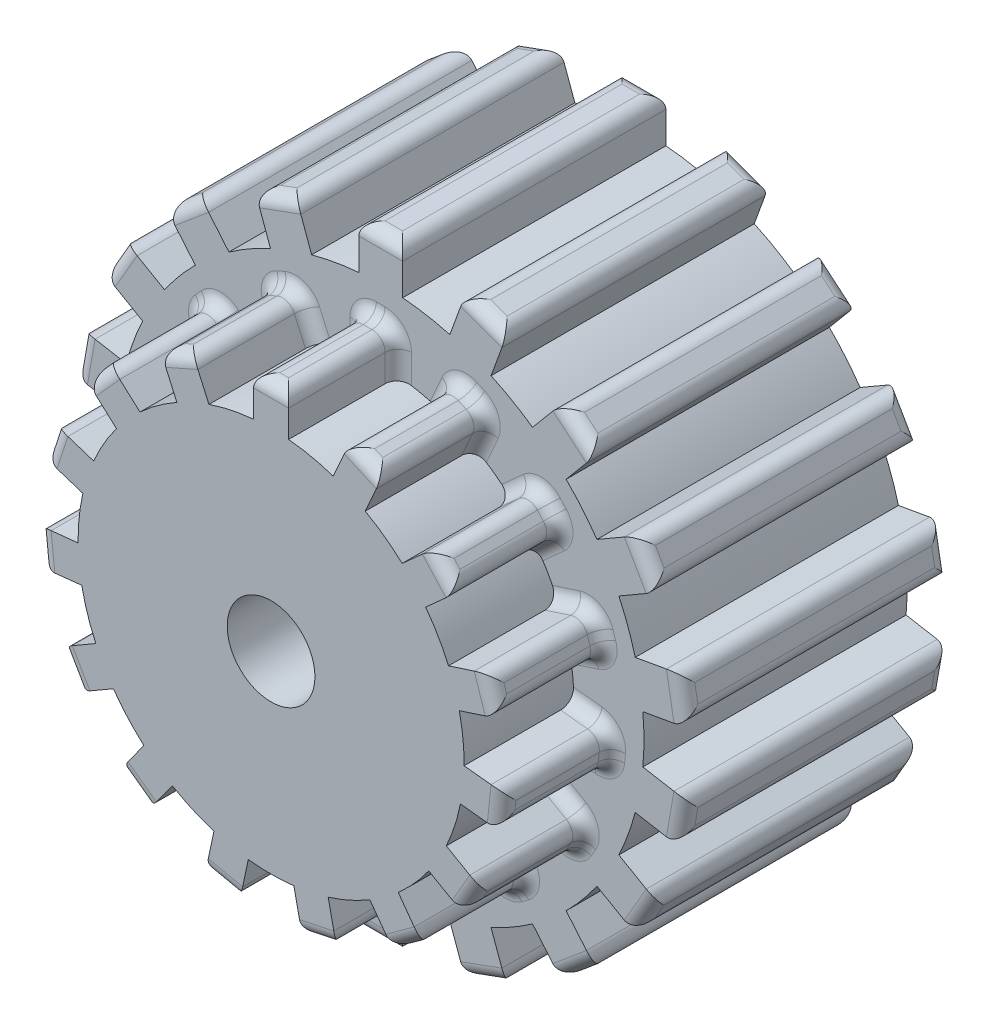
SolidWorks part; units mm, degrees
ref_plane "Front Plane" through (0, 0, 0) normal (0, 0, 1) x (1, 0, 0)
ref_plane "Top Plane" through (0, 0, 0) normal (0, 1, 0) x (1, 0, 0)
ref_plane "Right Plane" through (0, 0, 0) normal (1, 0, 0) x (0, 0, -1)
sketch "Sketch2" plane through (0, 0, 0) normal (0, 0, 1) x (1, 0, 0)
  circle A0 centre (0, 0) radius 60
extrude "Boss-Extrude1" add sketch "Sketch2" along normal blind 60
sketch "Sketch3" plane through (0, 0, 60) normal (0, 0, 1) x (1, 0, 0)
  line L0 (0, 60) -> (0, 70) construction
  line L1 (5, 70) -> (-5, 70)
  line L2 (-5, 70) -> (-5, 59.5215)
  line L3 (-5, 59.5215) -> (5, 59.5215)
  line L4 (5, 59.5215) -> (5, 70)
  circle A0 centre (0, 0) radius 60 construction
  point P9 (0, 70)
extrude "Boss-Extrude2" add sketch "Sketch3" against normal blind 60
fillet "Fillet2" radius 3 4 edges at (-5, 70, 30) (0, 70, 0) (5, 70, 30) (0, 70, 60)
pattern_circular "CirPattern1" count 18 over 360 about axis through (0, 0, 60) along (0, 0, -1) of "Fillet2", "Boss-Extrude2" reverse direction yes
sketch "Sketch4" plane through (0, 0, 60) normal (0, 0, 1) x (1, 0, 0)
  circle A0 centre (0, 0) radius 10
extrude "Cut-Extrude1" cut sketch "Sketch4" against normal blind 60
sketch "Sketch5" plane through (0, 0, 60) normal (0, 0, 1) x (1, 0, 0)
  circle A0 centre (0, 0) radius 44
extrude "Boss-Extrude3" add sketch "Sketch5" along normal blind 25
sketch "Sketch6" plane through (0, 0, 85) normal (0, 0, 1) x (1, 0, 0)
  line L0 (0, 44) -> (0, 53) construction
  line L1 (4, 53) -> (-4, 53)
  line L2 (-4, 53) -> (-4, 42.9556)
  line L3 (-4, 42.9556) -> (4, 42.9556)
  line L4 (4, 42.9556) -> (4, 53)
  circle A0 centre (0, 0) radius 44 construction
  circle A1 centre (0, 0) radius 44 construction
  point P10 (0, 53)
extrude "Boss-Extrude4" add sketch "Sketch6" against normal blind 25
sketch "Sketch7" plane through (0, 0, 0) normal (0, 0, -1) x (-1, 0, 0)
  circle A0 centre (0, 0) radius 10
extrude "Cut-Extrude2" cut sketch "Sketch7" against normal blind 90
fillet "Fillet3" radius 3 6 edges at (-4, 48.4089, 60) (4, 48.4089, 60) (-4, 53, 72.5) (0, 53, 60) (4, 53, 72.5) (0, 53, 85)
pattern_circular "CirPattern2" count 15 over 360 about axis through (0, 0, 85) along (0, 0, -1) of "Boss-Extrude4", "Fillet3" reverse direction yes
